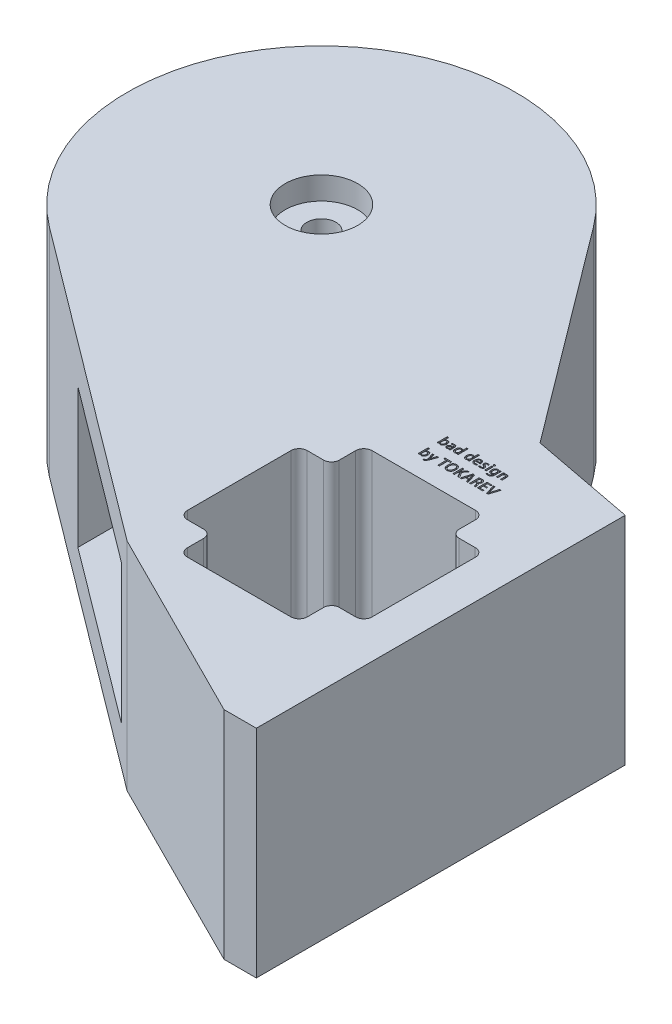
SolidWorks part; units mm, degrees
ref_plane "Front Plane" through (0, 0, 0) normal (0, 0, 1) x (1, 0, 0)
ref_plane "Top Plane" through (0, 0, 0) normal (0, 1, 0) x (1, 0, 0)
ref_plane "Right Plane" through (0, 0, 0) normal (1, 0, 0) x (0, 0, -1)
sketch "Эскиз1" plane through (0, 0, 0) normal (0, 1, 0) x (1, 0, 0)
  line L0 (0, -60) -> (120, -60) construction
  line L1 (60, -60) -> (120, -60)
  line L2 (120, -60) -> (120, -120)
  line L3 (120, -120) -> (60, -120)
  line L4 (60, -120) -> (60, -60)
  line L5 (60, -120) -> (-36, -48)
  line L6 (120, -60) -> (48, 36)
  line L7 (130, -36.1984) -> (97.5, -30)
  line L8 (120, -36.1984) -> (130, -36.1984)
  line L9 (120, -36.1984) -> (120, -150.1)
  line L10 (120, -150.1) -> (130, -150.1)
  line L11 (130, -36.1984) -> (130, -150.1)
  line L12 (120, -150.1) -> (90, -120)
  line L13 (120, -150.1) -> (120, -120)
  line L14 (120, -60) -> (120, -36.1984)
  line L15 (60, -120) -> (120, -150.1)
  circle A0 centre (0, 0) radius 60
  dimension "D1" = 120
  dimension "D2" = 60
  dimension "D3" = 60
  dimension "D4" = 30
  dimension "D5" = 10
  dimension "D6" = 113.9016
  dimension "D7" = 30.1
extrude "Бобышка-Вытянуть1" add sketch "Эскиз1" along normal blind 66.8 contours L4 L3 L2 L1 | L0 A0 L5 L4 | A0 L0 L1 L6 | A0 | L12 L9 L3 | L11 L8 L9 L2 L10 | L9 L8 L7 L6 | L3 L15 L12 region at (71.6805, 0, 35.8402) region at (32.4364, 0, 79.6167) region at (0, 0, 0) region at (90, 0, 90) region at (125, 0, 93.1492) region at (112.8458, 0, 41.2431) region at (90, 0, 130.0333) region at (110, 0, 130.0333)
sketch "Эскиз3" plane through (0, 66.8, 0) normal (0, 1, 0) x (1, 0, 0)
  line L0 (71.1, -112.5) -> (71.1, -107.5)
  line L1 (61.1, -58) -> (118.1, -58)
  line L2 (61.1, -58) -> (61.1, -115)
  line L3 (61.1, -115) -> (118.1, -115)
  line L4 (118.1, -58) -> (118.1, -115)
  line L5 (71.1, -60.6067) -> (71.1, -65.6067)
  line L6 (63.7067, -105) -> (68.7067, -105)
  line L7 (61.1, -58) -> (73.6, -58)
  line L8 (61.1, -58) -> (61.1, -70.5)
  line L9 (61.1, -70.5) -> (73.6, -70.5)
  line L10 (73.6, -58) -> (73.6, -70.5)
  line L11 (63.6, -68) -> (68.6, -68)
  line L12 (115.6, -105) -> (110.6, -105)
  line L13 (61.1, -58) -> (118.1, -115) construction
  line L14 (108.1, -112.3933) -> (108.1, -107.3933)
  line L15 (108.1, -60.5) -> (108.1, -65.5)
  line L16 (115.4933, -68) -> (110.4933, -68)
  line L17 (120, -120) -> (60, -120) construction
  arc A0 (61.1, -70.5) -> (63.6, -68) centre (63.6, -70.5) cw
  arc A1 (73.6, -58) -> (71.1, -60.6067) centre (73.6534, -60.5534) ccw
  arc A2 (71.1, -65.6067) -> (68.6, -68) centre (68.6534, -65.5534) cw
  arc A3 (61.1, -102.5) -> (63.7067, -105) centre (63.6534, -102.4466) ccw
  arc A4 (73.6, -115) -> (71.1, -112.5) centre (73.6, -112.5) cw
  arc A5 (68.7067, -105) -> (71.1, -107.5) centre (68.6534, -107.4466) cw
  arc A6 (105.6, -115) -> (108.1, -112.3933) centre (105.5466, -112.4466) ccw
  arc A7 (118.1, -102.5) -> (115.6, -105) centre (115.6, -102.5) cw
  arc A8 (108.1, -107.3933) -> (110.6, -105) centre (110.5466, -107.4466) cw
  arc A9 (118.1, -70.5) -> (115.4933, -68) centre (115.5466, -70.5534) ccw
  arc A10 (105.6, -58) -> (108.1, -60.5) centre (105.6, -60.5) cw
  arc A11 (110.4933, -68) -> (108.1, -65.5) centre (110.5466, -65.5534) cw
  point P46 (89.6, -86.5)
  point P64 (73.6, -60.5)
  dimension "D7" = 2.5
  dimension "D8" = 10.6821
  dimension "D11" = 5
  dimension "D1" = 57
  dimension "D3" = 4
  dimension "D4" = 57
  dimension "D5" = 12.5
  dimension "D6" = 12.5
  dimension "D9" = 5
  dimension "D10" = 5
  dimension "D12" = 90
  dimension "D13" = 90
  dimension "D14" = 90
  dimension "D15" = 2.5
extrude "Вырез-Вытянуть1" cut sketch "Эскиз3" against normal blind 53 contours L1 L10 L9 L2 L3 L4 | L10 L13 A8 L12 A7 L4 A9 L16 A11 L15 A10 L1 | A2 L13 L10 A1 L5 | L13 A2 L11 A0 L9 region at (80.815, 66.8, 96.065) region at (67.0784, 66.8, 69.2969) region at (99.1654, 66.8, 77.7156) region at (72.3978, 66.8, 63.9889)
sketch "Эскиз4" plane through (0, 66.8, 0) normal (0, 1, 0) x (1, 0, 0)
  line L0 (0, 0) -> (-37.8894, 46.523) construction
  arc A0 (48, 36) -> (-36, -48) centre (0, 0) ccw construction
sketch "Эскиз6" plane through (0, 66.8, 0) normal (0, 1, 0) x (1, 0, 0)
  circle A0 centre (0, 0) radius 4.5
  dimension "D1" = 9
extrude "Вырез-Вытянуть2" cut sketch "Эскиз6" against normal blind 73
sketch "Эскиз11" plane through (0, 66.8, 0) normal (0, 1, 0) x (1, 0, 0)
  circle A0 centre (0, 0) radius 11.2
  dimension "D1" = 22.4
sketch "Эскиз12" plane through (0, 0, 0) normal (0, -1, 0) x (1, 0, 0)
  circle A0 centre (0, 0) radius 11.2
  dimension "D1" = 22.4
extrude "Вырез-Вытянуть3" cut sketch "Эскиз11" against normal blind 7
extrude "Вырез-Вытянуть4" cut sketch "Эскиз12" against normal blind 7 contours A0
sketch "Эскиз18" plane through (0, 66.8, 0) normal (0, 1, 0) x (1, 0, 0)
  line L0 (87.6366, -91.7125) -> (-19.364, -51.409)
  line L1 (50.6956, 21.1614) -> (94.7402, -84.3544)
  circle A0 centre (89.6, -86.5) radius 5.57
  circle A1 centre (0, 0) radius 54.935
  arc A2 (50.6956, 21.1614) -> (-19.364, -51.409) centre (0, 0) ccw
  arc A3 (87.6366, -91.7125) -> (94.7402, -84.3544) centre (89.6, -86.5) ccw
  dimension "D1" = 109.87
  dimension "D2" = 11.14
sketch "Эскиз19" plane through (0, 66.8, 0) normal (0, 1, 0) x (1, 0, 0)
  text T0 "<b>bad design</b>\r\n<b>by TOKAREV</b>" font "Adobe Heiti Std R" height 3
extrude "Вырез-Вытянуть5" cut sketch "Эскиз19" against normal blind 0.4
sketch "Эскиз20" plane through (-36, 0, 48) normal (-0.6, 0, 0.8) x (0.8, 0, 0.6)
  line L0 (44, 54.9) -> (44, 66.8) construction
  line L1 (44, 54.9) -> (111, 54.9)
  line L2 (44, 54.9) -> (44, 11.9)
  line L3 (44, 11.9) -> (111, 11.9)
  line L4 (111, 54.9) -> (111, 11.9)
  line L5 (120, 66.8) -> (0, 66.8) construction
  line L6 (0, 66.8) -> (0, 0) construction
  line L7 (44, 11.9) -> (44, 0) construction
  line L8 (120, 0) -> (0, 0) construction
  dimension "D1" = 67
  dimension "D2" = 43
  dimension "D3" = 44
sketch "Эскиз21" plane through (0, 66.8, 0) normal (0, 1, 0) x (1, 0, 0)
  line L0 (26, -94.5) -> (26, -25.5)
  line L1 (-0.8, -74.4) -> (52.8, -114.6) construction
  dimension "D1" = 69
sweep "Вырез-По траектории1" cut profiles "Эскиз20" path "Эскиз21"
